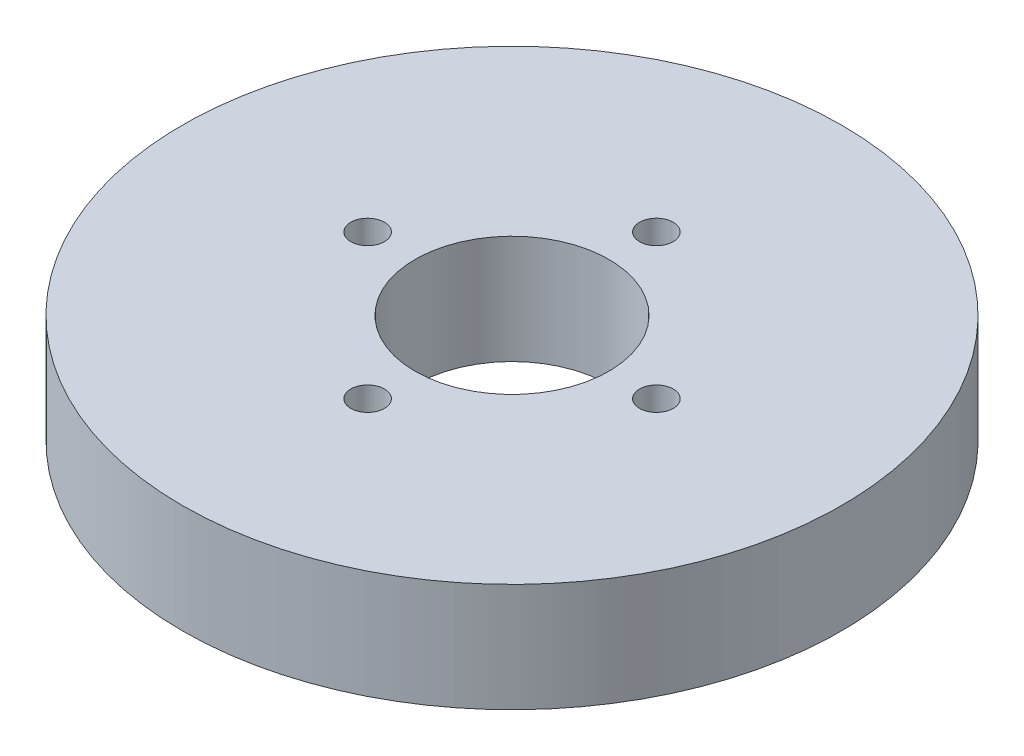
SolidWorks part; units mm, degrees
ref_plane "Front Plane" through (0, 0, 0) normal (0, 0, 1) x (1, 0, 0)
ref_plane "Top Plane" through (0, 0, 0) normal (0, 1, 0) x (1, 0, 0)
ref_plane "Right Plane" through (0, 0, 0) normal (1, 0, 0) x (0, 0, -1)
sketch "Sketch1" plane through (0, 0, 0) normal (0, 1, 0) x (1, 0, 0)
  circle A0 centre (0, 0) radius 42.5
  dimension "FLANGE_OD" = 85
extrude "Boss-Extrude1" add sketch "Sketch1" along normal blind 14
sketch "Sketch2" plane through (0, 0, 0) normal (0, 1, 0) x (1, 0, 0)
  circle A0 centre (0, 0) radius 12.5
  dimension "BORE_D" = 25
extrude "Cut-Extrude1" cut sketch "Sketch2" along normal through all
sketch "Sketch3" plane through (0, 14, 0) normal (0, 1, 0) x (1, 0, 0)
  circle A0 centre (0, 0) radius 18.6195 construction
  circle A1 centre (-18.6195, 0) radius 2.1731
  dimension "BOLT_D" = 4.3461
  dimension "BOLT_PCD" = 37.2391
extrude "Cut-Extrude2" cut sketch "Sketch3" against normal blind 9.2782
pattern_circular "CirPattern1" count 4 over 360 about axis through (0, 0, 0) along (0, 1, 0) of "Cut-Extrude2"
